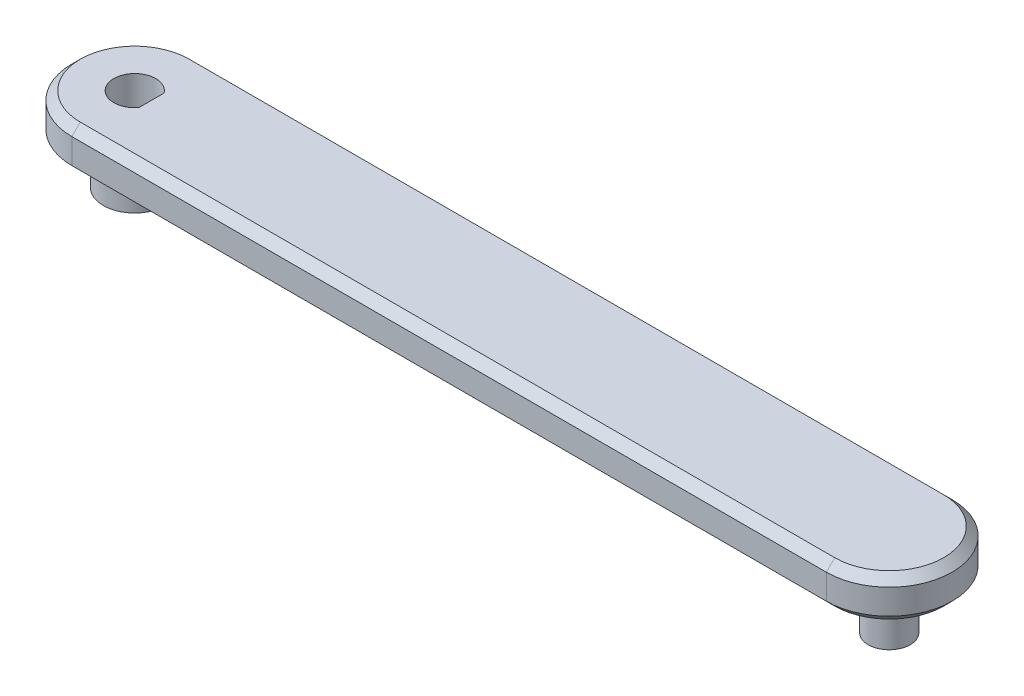
SolidWorks part; units mm, degrees
ref_plane "前视基准面" through (0, 0, 0) normal (0, 0, 1) x (1, 0, 0)
ref_plane "上视基准面" through (0, 0, 0) normal (0, 1, 0) x (1, 0, 0)
ref_plane "右视基准面" through (0, 0, 0) normal (1, 0, 0) x (0, 0, -1)
other "Configuration Table"
sketch "草图1" plane through (0, 0, 0) normal (0, 1, 0) x (1, 0, 0)
  line L0 (0, 0) -> (180, 0) construction
  line L1 (0, 15) -> (180, 15)
  line L2 (0, -15) -> (180, -15)
  arc A0 (0, 15) -> (0, -15) centre (0, 0) ccw
  arc A1 (180, -15) -> (180, 15) centre (180, 0) ccw
  circle A2 centre (180, 0) radius 5
  point P3 (90, 0)
  dimension "D2" = 15
  dimension "D3" = 10
  dimension "D1" = 180
extrude "凸台-拉伸2" add sketch "草图1" along normal blind 10 contours A1 L1 A0 L2
sketch "草图9" plane through (0, 0, 0) normal (0, -1, 0) x (1, 0, 0)
  circle A0 centre (0, 0) radius 7.5
  dimension "D1" = 15
chamfer "倒角1" distance 2 angle 45 8 edges at (-15, 10, 0) (90, 10, 15) (90, 10, -15) (195, 10, 0) (195, 0, 0) (90, 0, 15) (-15, 0, 0) (90, 0, -15)
sketch "草图4" plane through (0, 0, 0) normal (0, -1, 0) x (1, 0, 0)
  line L0 (4, 3) -> (4, -3)
  arc A0 (4, 3) -> (4, -3) centre (0, 0) ccw
  point P5 (0, 0)
  dimension "D1" = 10
  dimension "D2" = 4
extrude "凸台-拉伸7" add sketch "草图9" along normal blind 10
extrude "切除-拉伸3" cut sketch "草图4" against normal through all and the other way blind 10 contours A0 L0
sketch "草图11" plane through (0, 0, 0) normal (0, -1, 0) x (1, 0, 0)
  circle A0 centre (180, 0) radius 5
  point P3 (0, 0)
  dimension "D1" = 10
extrude "凸台-拉伸8" add sketch "草图11" along normal blind 12
